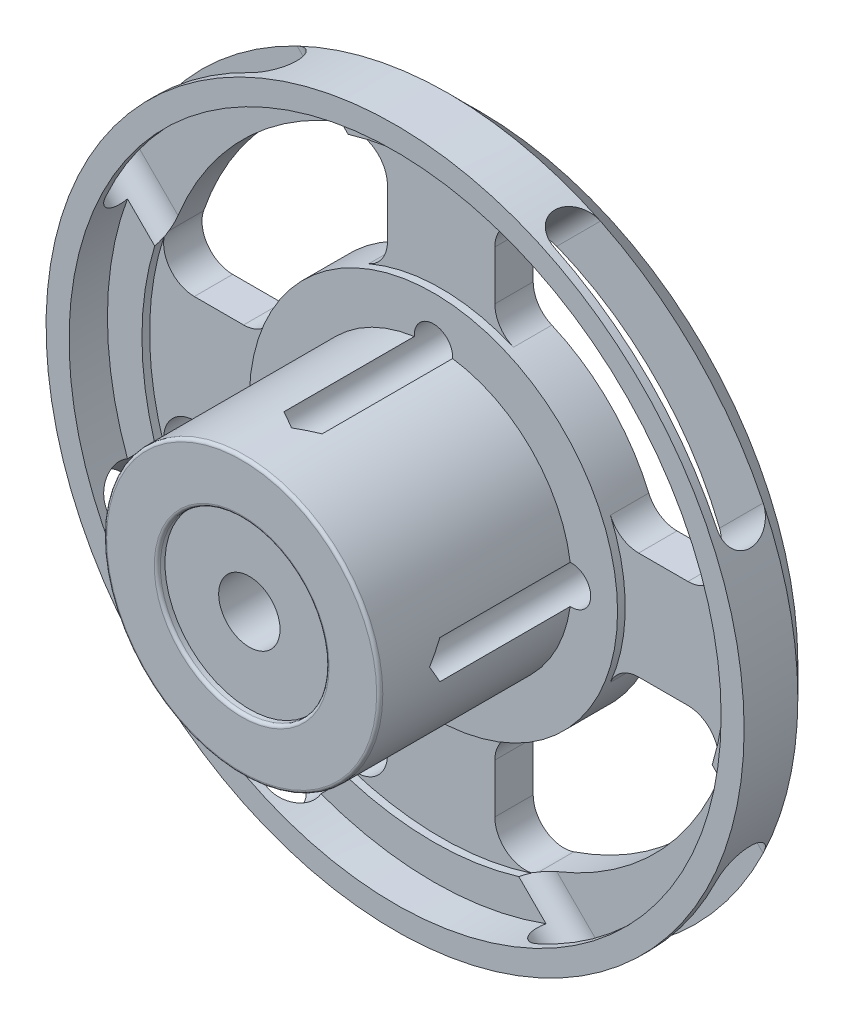
SolidWorks part; units mm, degrees
ref_plane "Спереди" through (0, 0, 0) normal (0, 0, 1) x (1, 0, 0)
ref_plane "Сверху" through (0, 0, 0) normal (0, 1, 0) x (1, 0, 0)
ref_plane "Справа" through (0, 0, 0) normal (1, 0, 0) x (0, 0, -1)
sketch "Эскиз1" plane through (0, 0, 0) normal (0, 0, 1) x (1, 0, 0)
  circle A0 centre (0, 0) radius 22.75
  dimension "D1" = 45.5
extrude "Бобышка-Вытянуть1" add sketch "Эскиз1" along normal blind 5.5
sketch "Эскиз2" plane through (0, 0, 5.5) normal (0, 0, 1) x (1, 0, 0)
  circle A0 centre (0, 0) radius 21.25
  circle A1 centre (0, 0) radius 22.75 construction
  dimension "D1" = 1.5
extrude "Вырез-Вытянуть1" cut sketch "Эскиз2" against normal offset from surface (2.5 mm away) 3 up to face at (22.75, 0, 0)
sketch "Эскиз3" plane through (0, 0, 0) normal (0, 0, -1) x (-1, 0, 0)
  circle A0 centre (0, 0) radius 12
  circle A1 centre (0, 0) radius 19
  dimension "D1" = 24
  dimension "D2" = 38
extrude "Вырез-Вытянуть2" cut sketch "Эскиз3" against normal through all
sketch "Эскиз4" plane through (0, 0, 0) normal (0, 0, -1) x (-1, 0, 0)
  line L1 (-3.5, 20.3584) -> (3.5, 20.3584)
  line L2 (-3.5, 20.3584) -> (-3.5, 3.5)
  line L3 (-3.5, -20.3584) -> (3.5, -20.3584)
  line L4 (3.5, 20.3584) -> (3.5, 3.5)
  line L5 (-3.5, 20.3584) -> (3.5, -20.3584) construction
  line L6 (-3.5, -20.3584) -> (3.5, 20.3584) construction
  line L7 (-20.0035, 3.5) -> (-3.5, 3.5)
  line L8 (-20.0035, 3.5) -> (-20.0035, -3.5)
  line L9 (-20.0035, -3.5) -> (-3.5, -3.5)
  line L10 (20.0035, 3.5) -> (20.0035, -3.5)
  line L11 (-20.0035, 3.5) -> (20.0035, -3.5) construction
  line L12 (-20.0035, -3.5) -> (20.0035, 3.5) construction
  line L13 (-3.5, -3.5) -> (-3.5, -20.3584)
  line L14 (3.5, -3.5) -> (3.5, -20.3584)
  line L15 (3.5, -3.5) -> (20.0035, -3.5)
  line L16 (3.5, 3.5) -> (20.0035, 3.5)
  point P0 (0, 0)
  point P6 (0, 0)
  dimension "D1" = 7
  dimension "D2" = 7
extrude "Бобышка-Вытянуть2" add sketch "Эскиз4" against normal blind 2.5
sketch "Эскиз5" plane through (0, 0, 3) normal (0, 0, 1) x (1, 0, 0)
  circle A0 centre (0, 0) radius 9
  dimension "D1" = 18
extrude "Бобышка-Вытянуть3" add sketch "Эскиз5" along normal offset from surface (12.5 mm away) 15.5 up to face at (-10.1242, 10.1242, 0)
sketch "Эскиз6" plane through (0, 0, 15.5) normal (0, 0, 1) x (1, 0, 0)
  circle A0 centre (0, 0) radius 5.5
  dimension "D1" = 11
extrude "Вырез-Вытянуть3" cut sketch "Эскиз6" against normal blind 0.5
sketch "Эскиз7" plane through (0, 0, 0) normal (0, 0, -1) x (-1, 0, 0)
  circle A0 centre (0, 0) radius 5.5
  dimension "D1" = 11
extrude "Вырез-Вытянуть4" cut sketch "Эскиз7" against normal blind 0.5
sketch "Эскиз8" plane through (0, 0, 0.5) normal (0, 0, -1) x (-1, 0, 0)
  circle A0 centre (0, 0) radius 2
  dimension "D1" = 4
extrude "Вырез-Вытянуть5" cut sketch "Эскиз8" against normal through all
sketch "Эскиз9" plane through (0, 0, 0) normal (0, 0, -1) x (-1, 0, 0)
  line L0 (-26.1336, 0) -> (26.8434, 0) construction
  line L1 (0, 24.101) -> (0, -24.7462) construction
  circle A0 centre (0, 0) radius 9 construction
  dimension "D1" = 18
hole_wizard "Отверстие обработанное метчиком M3x0.51" positions "Эскиз11" profile "Эскиз10" tap size "M3x0.5" standard "Ansi Metric"
sketch "Эскиз11" plane through (0, 0, 0) normal (0, 0, -1) x (-1, 0, 0)
  line L0 (0, 24.101) -> (0, -24.7462) construction
  line L1 (-26.1336, 0) -> (26.8434, 0) construction
  circle A0 centre (0, 0) radius 9 construction
  point P0 (0, 9)
  point P6 (0, -9)
  point P8 (9, 0)
  point P12 (-9, 0)
sketch "Эскиз10" plane through (0, 9, 0) normal (1, 0, 0) x (0, 1, 0)
  line L0 (0, 0) -> (0, 12.2511)
  line L1 (0, 12.2511) -> (1.25, 11.5)
  line L2 (1.25, 11.5) -> (1.25, 0)
  line L5 (1.25, 0) -> (0, 0)
  line L10 (0, 12.2511) -> (-1.25, 11.5) construction
  line L11 (0, -6.35) -> (0, 107.95) construction
  dimension "Диаметр сверла" = 2.5
  dimension "Глубина сверла" = 11.5
  dimension "Угол заточки сверла" = 118
cosmetic thread "Отверстие резьбы1" parameters "D1"=8, "D2"=3
cosmetic thread "Отверстие резьбы2" parameters "D1"=8, "D2"=3
cosmetic thread "Отверстие резьбы3" parameters "D1"=8, "D2"=3
cosmetic thread "Отверстие резьбы4" parameters "D1"=8, "D2"=3
chamfer "Фаска1" distance 2 angle 45 1 edges at (22.75, 0, 0)
fillet "Скругление1" radius 2 16 edges at (-18.6748, -3.5, 1.25) (-11.4782, -3.5, 1.25) (-3.5, -18.6748, 1.25) (-3.5, -11.4782, 1.25) (3.5, -18.6748, 1.25) (18.6748, -3.5, 1.25) (3.5, -11.4782, 1.25) (11.4782, -3.5, 1.25) (3.5, 18.6748, 1.25) (18.6748, 3.5, 1.25) (11.4782, 3.5, 1.25) (3.5, 11.4782, 1.25) (-3.5, 18.6748, 1.25) (-3.5, 11.4782, 1.25) (-11.4782, 3.5, 1.25) (-18.6748, 3.5, 1.25)
ref_plane "Плоскость1" through (16.0867, -16.0867, 0) normal (0.7071, -0.7071, 0) x (0, 0, 1)
sketch "Эскиз12" plane through (16.0867, -16.0867, 0) normal (0.7071, -0.7071, 0) x (0, 0, 1)
  line L0 (18.2891, 0) -> (-11.2891, 0) construction
  line L1 (3.5, -7.5) -> (3.5, 7.5) construction
  line L2 (2, -7.5) -> (2, 7.5)
  line L3 (5, -7.5) -> (5, 7.5)
  line L4 (2, -22.75) -> (2, 22.75) construction
  arc A0 (2, -7.5) -> (5, -7.5) centre (3.5, -7.5) ccw
  arc A1 (5, 7.5) -> (2, 7.5) centre (3.5, 7.5) ccw
  point P5 (3.5, 0)
  dimension "D1" = 1.5
  dimension "D2" = 15
extrude "Вырез-Вытянуть6" cut sketch "Эскиз12" against normal blind 7
ref_axis "Ось1" through (0, 0, 15) along (0, 0, -1)
pattern_circular "Круговой массив1" count 4 every 90 about axis through (0, 0, 15) along (0, 0, -1) of "Вырез-Вытянуть6"
fillet "Скругление2" radius 0.2 2 edges at (9, 0, 15.5) (5.5, 0, 15.5)
